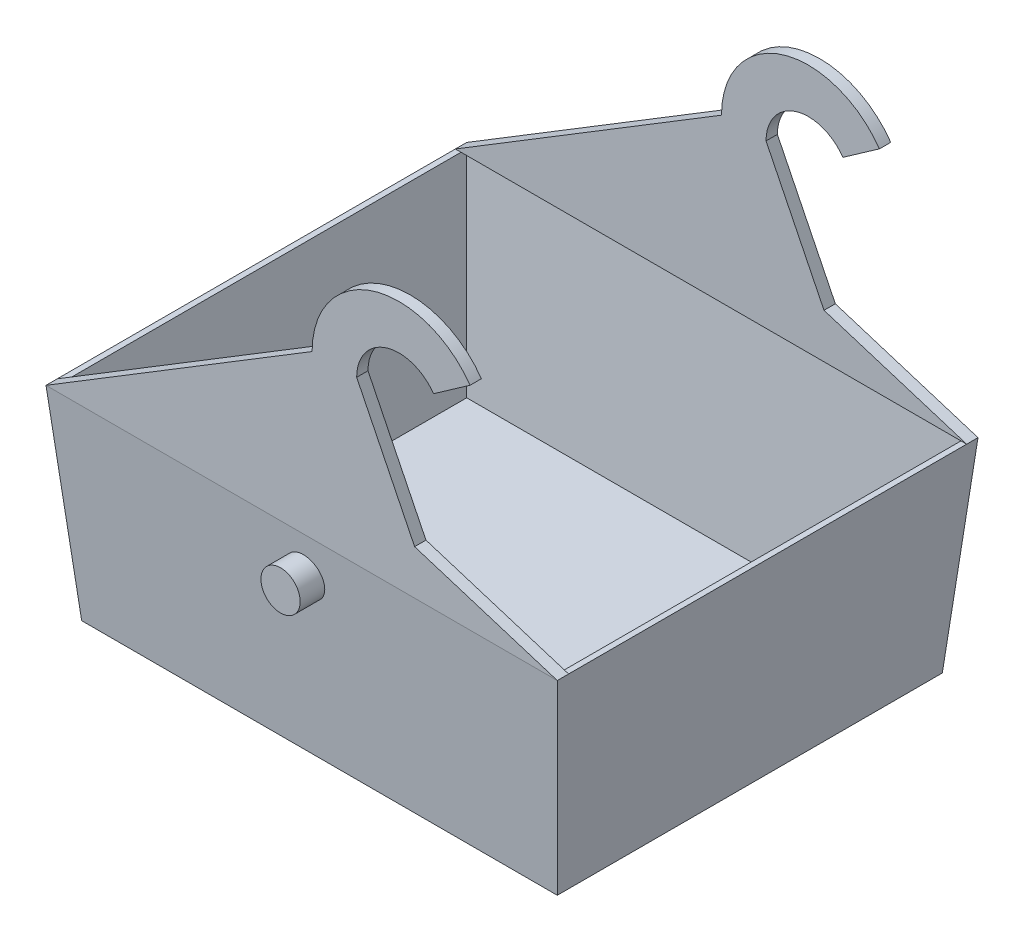
SolidWorks part; units mm, degrees
other "Markup1"
sketch "Sketch8"
ref_plane "Front Plane" through (0, 0, 0) normal (0, 0, 1) x (1, 0, 0)
ref_plane "Top Plane" through (0, 0, 0) normal (0, 1, 0) x (1, 0, 0)
ref_plane "Right Plane" through (0, 0, 0) normal (1, 0, 0) x (0, 0, -1)
sketch "Sketch1" plane through (0, 0, 0) normal (0, 1, 0) x (1, 0, 0)
  line L1 (-133.35, -107.95) -> (133.35, -107.95)
  line L2 (-133.35, -107.95) -> (-133.35, 107.95)
  line L3 (-133.35, 107.95) -> (133.35, 107.95)
  line L4 (133.35, -107.95) -> (133.35, 107.95)
  line L5 (-133.35, -107.95) -> (133.35, 107.95) construction
  line L6 (-133.35, 107.95) -> (133.35, -107.95) construction
  line L7 (-130.175, -104.775) -> (130.175, -104.775)
  line L8 (-130.175, -104.775) -> (-130.175, 104.775)
  line L9 (-130.175, 104.775) -> (130.175, 104.775)
  line L10 (130.175, -104.775) -> (130.175, 104.775)
  line L11 (-130.175, -104.775) -> (130.175, 104.775) construction
  line L12 (-130.175, 104.775) -> (130.175, -104.775) construction
  point P0 (0, 0)
  point P6 (0, 0)
  dimension "D1" = 266.7
  dimension "D2" = 215.9
  dimension "D3" = 3.175
  dimension "D4" = 3.175
extrude "Boss-Extrude1" add sketch "Sketch1" along normal blind 114.3 draft 5 draft outward yes
extrude "Boss-Extrude2" add sketch "Sketch1<5>" along normal blind 3.175 draft 5 contours L7 L10 L9 L8 region at (0, 0, 0) draft outward yes
sketch "Sketch1<5>" plane through (0, 0, 0) normal (0, 1, 0) x (1, 0, 0) same geometry as "Sketch1"
sketch "Sketch3" plane through (0, 114.3, 0) normal (0, 1, 0) x (1, 0, 0)
  line L1 (-143.35, -117.95) -> (143.35, -117.95)
  line L2 (-143.35, -117.95) -> (-143.35, 117.95)
  line L3 (-143.35, 117.95) -> (143.35, 117.95)
  line L4 (143.35, -117.95) -> (143.35, 117.95)
  line L5 (-143.35, -117.95) -> (143.35, 117.95) construction
  line L6 (-143.35, 117.95) -> (143.35, -117.95) construction
  line L7 (-140.175, -114.775) -> (140.175, -114.775)
  line L8 (-140.175, -114.775) -> (-140.175, 114.775)
  line L9 (-140.175, 114.775) -> (140.175, 114.775)
  line L10 (140.175, -114.775) -> (140.175, 114.775)
  line L11 (-140.175, -114.775) -> (140.175, 114.775) construction
  line L12 (-140.175, 114.775) -> (140.175, -114.775) construction
  point P0 (0, 0)
  point P7 (0, 0)
  line M9 (120.175, 94.775) -> (120.175, -94.775)
  line M10 (120.175, -94.775) -> (-120.175, -94.775)
  line M11 (-120.175, -94.775) -> (-120.175, 94.775)
  line M12 (-120.175, 94.775) -> (120.175, 94.775)
  dimension "D1" = 3.175
  dimension "D2" = 3.175
extrude "Cut-Extrude1" cut sketch "Sketch3" against normal blind 111.125 draft 5 contours L7 L10 L9 L8 M12 M9 M10 M11 region at (-136.5516, 114.3, 0)
ref_plane "Plane2" through (0, 0, -114.775) normal (0, 0, 1) x (1, 0, 0)
ref_plane "Plane3" through (0, 0, -117.95) normal (0, 0, 1) x (1, 0, 0)
sketch "Sketch5" plane through (0, 0, 0) normal (0, 0, 1) x (1, 0, 0)
  line L0 (-143.35, 114.3) -> (5.85, 205.3)
  line L1 (-143.35, 114.3) -> (143.35, 114.3) construction
  line L2 (-143.35, 114.3) -> (-133.35, 0) construction
  line L3 (30.85, 205.3) -> (63.35, 139.3)
  line L4 (63.35, 139.3) -> (143.35, 114.3)
  line L5 (73.9639, 218.8938) -> (94.4427, 233.2332)
  line L6 (18.35, 541.0668) -> (18.35, -49458.9332) construction
  line L7 (18.35, 205.3) -> (30.85, 205.3) construction
  line L8 (5.85, 205.3) -> (18.35, 205.3) construction
  line L9 (-133.35, 0) -> (133.35, 0) construction
  line L10 (-307.1062, 254) -> (49692.8938, 254) construction
  line L11 (-143.35, 114.3) -> (143.35, 114.3)
  arc A0 (30.85, 205.3) -> (73.9639, 218.8938) centre (54.55, 205.3) cw
  arc A1 (5.85, 205.3) -> (94.4427, 233.2332) centre (54.55, 205.3) cw
  dimension "D1" = 23.7
  dimension "D2" = 25
  dimension "D3" = 254
  dimension "D4" = 145
  dimension "D5" = 125
  dimension "D6" = 25
  dimension "D7" = 80
extrude "Boss-Extrude3" add sketch "Sketch5" against normal up to surface (117.95 mm away) and the other way blind 3.175 from surface up to plane "Plane3" starting at plane "Plane2"
sketch "Sketch7" plane through (0, 0, 0) normal (0, 0, 1) x (1, 0, 0)
  line L0 (-140.175, 114.3) -> (140.175, 114.3) construction
  circle A0 centre (0, 92.3) radius 11
  point P2 (0, 0)
  dimension "D1" = 22
  dimension "D2" = 22
extrude "Boss-Extrude4" add sketch "Sketch7" against normal blind 15 from surface starting at plane "Plane2"
mirror "Mirror5" about plane through (0, 0, 0) normal (0, 0, 1) of "Boss-Extrude4", "Boss-Extrude3"
